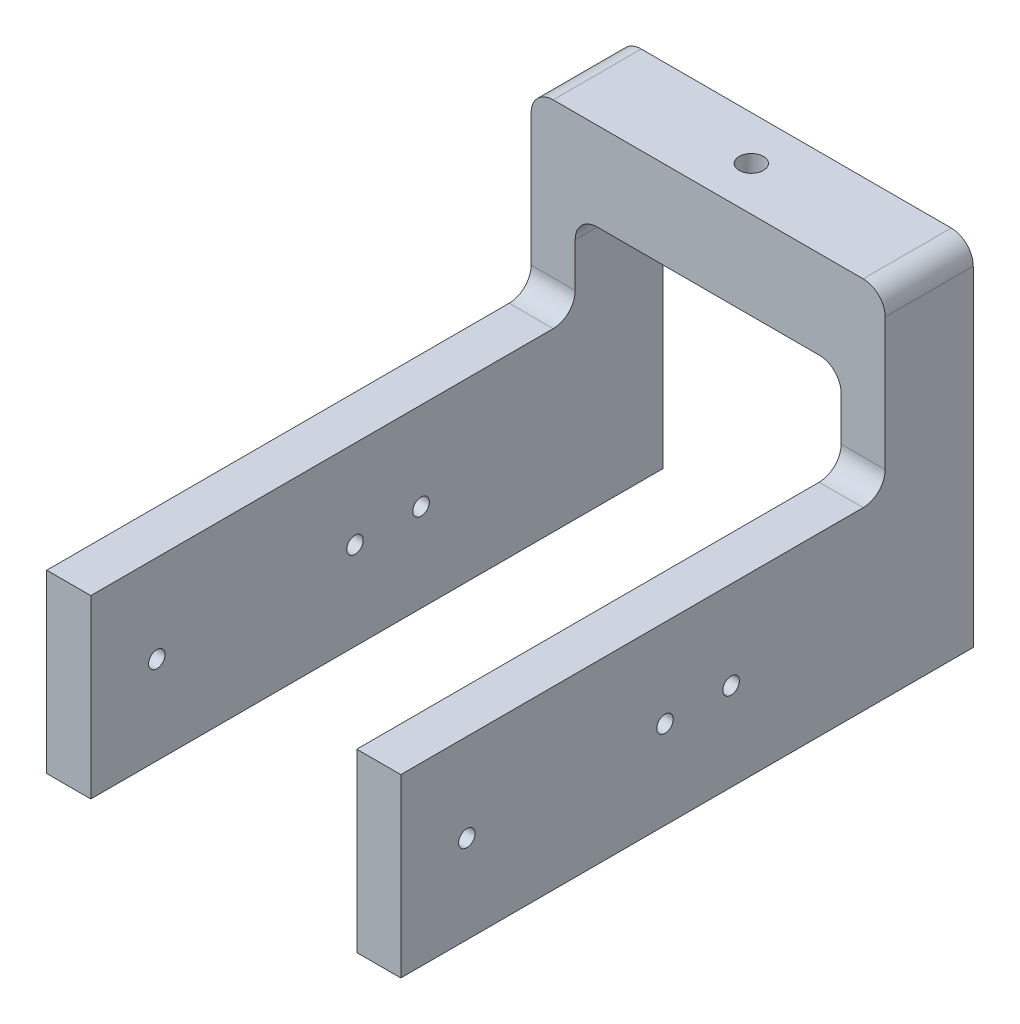
SolidWorks part; units mm, degrees
ref_plane "Front Plane" through (0, 0, 0) normal (0, 0, 1) x (1, 0, 0)
ref_plane "Top Plane" through (0, 0, 0) normal (0, 1, 0) x (1, 0, 0)
ref_plane "Right Plane" through (0, 0, 0) normal (1, 0, 0) x (0, 0, -1)
sketch "Sketch1" plane through (0, 0, 0) normal (1, 0, 0) x (0, 0, -1)
  line L0 (0, 0) -> (-165.1, 0)
  line L1 (-165.1, 0) -> (-165.1, 50.8)
  line L2 (-165.1, 50.8) -> (-25.4, 50.8)
  line L3 (-25.4, 50.8) -> (-25.4, 101.6)
  line L4 (-25.4, 101.6) -> (0, 101.6)
  line L5 (0, 101.6) -> (0, 0)
  point P7 (-12.7, 101.6)
  dimension "D1" = 152.4
  dimension "D2" = 50.8
  dimension "D3" = 101.6
  dimension "D4" = 25.4
extrude "Boss-Extrude1" add sketch "Sketch1" along normal blind 102.108
sketch "Sketch2" plane through (0, 0, 0) normal (0, 0, -1) x (-1, 0, 0)
  line L0 (-102.108, 0) -> (0, 0) construction
  line L1 (-89.408, 0) -> (-89.408, 76.2)
  line L2 (-89.408, 76.2) -> (-12.7, 76.2)
  line L3 (-12.7, 76.2) -> (-12.7, 0)
  line L4 (-12.7, 0) -> (-89.408, 0)
  line L5 (-102.108, 0) -> (-102.108, 101.6) construction
  line L6 (0, 0) -> (0, 101.6) construction
  line L7 (-102.108, 101.6) -> (0, 101.6) construction
  dimension "D1" = 12.7
  dimension "D2" = 12.7
  dimension "D3" = 25.4
extrude "Cut-Extrude1" cut sketch "Sketch2" against normal through all
hole_wizard "Ø7.0mm Dowel Hole1" positions "Sketch3" profile "Sketch4" hole size "Ø1.0" standard "ANSI Metric" end condition through all
sketch "Sketch3" plane through (0, 101.6, 0) normal (0, 1, 0) x (1, 0, 0)
  point P0 (50.8, -12.7)
  dimension "D1" = 50.8
  dimension "D2" = 12.7
sketch "Sketch4" plane through (50.8, 101.6, 12.7) normal (1, 0, 0) x (0, 0, 1)
  line L0 (0, 0) -> (0, 101.6)
  line L1 (0, 101.6) -> (3.5, 101.6)
  line L2 (3.5, 101.6) -> (3.5, 0)
  line L5 (3.5, 0) -> (0, 0)
  line L11 (0, -6.35) -> (0, 107.95) construction
  dimension "Thru Hole Dia." = 7
  dimension "Thru Hole Depth" = 101.6
fillet "Fillet1" radius 6.35 6 edges at (89.408, 76.2, 12.7) (12.7, 76.2, 12.7) (6.35, 50.8, 25.4) (95.758, 50.8, 25.4) (102.108, 101.6, 12.7) (0, 101.6, 12.7)
sketch "Sketch5" plane through (102.108, 0, 0) normal (1, 0, 0) x (0, 0, -1)
  line L0 (-165.1, 25.4) -> (0, 25.4) construction
  line L1 (-165.1, 50.8) -> (-165.1, 0) construction
  line L2 (0, 0) -> (0, 95.25) construction
  circle A0 centre (-146.05, 25.4) radius 2.3813
  circle A1 centre (-88.9, 25.4) radius 2.3813
  circle A2 centre (-69.85, 25.4) radius 2.3813
  point P15 (-168.0025, 50.1782)
  dimension "D1" = 4.7625
  dimension "D2" = 19.05
  dimension "D3" = 76.2
  dimension "D4" = 95.25
extrude "Cut-Extrude2" cut sketch "Sketch5" against normal through all
